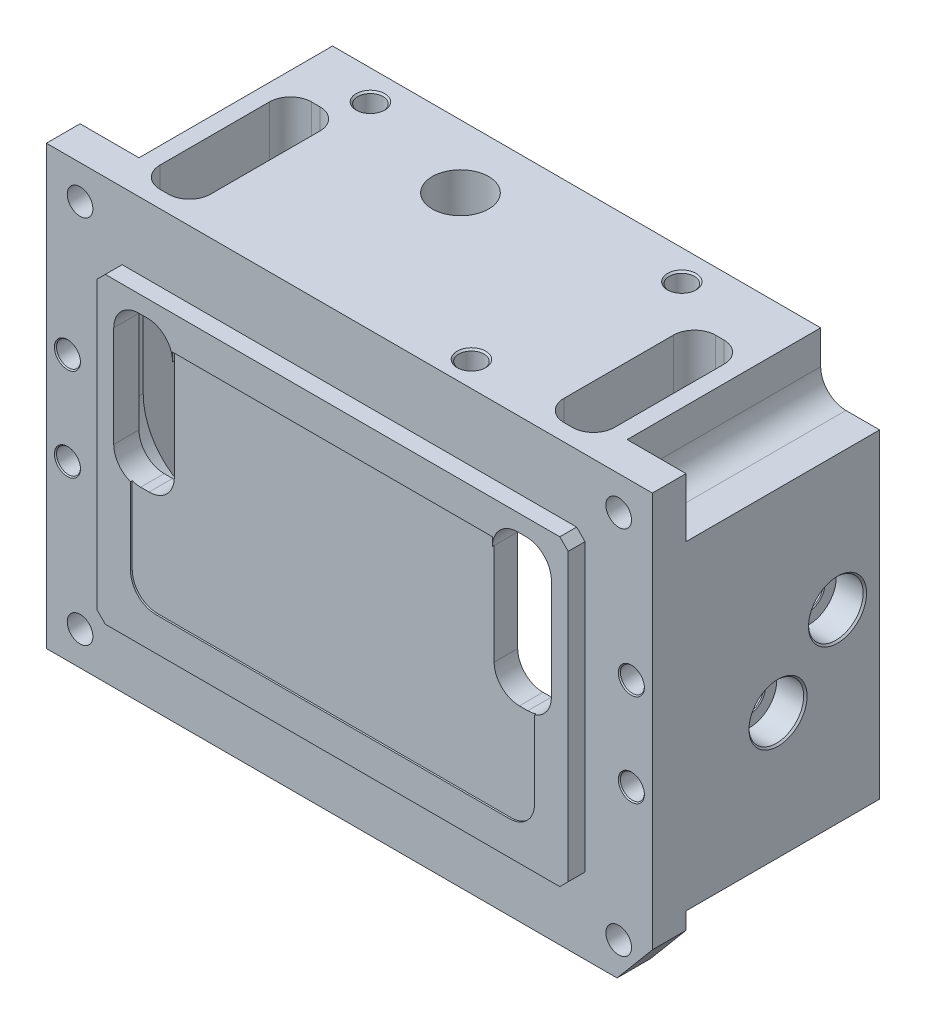
SolidWorks part; units mm, degrees
note: The reader was unsure of these and kept them because the rebuilt part matched: shared geometry of "Эскиз2<3>".
material "2024-T4"
ref_plane "Спереди" through (0, 0, 0) normal (0, 0, 1) x (1, 0, 0)
ref_plane "Сверху" through (0, 0, 0) normal (0, 1, 0) x (1, 0, 0)
ref_plane "Справа" through (0, 0, 0) normal (1, 0, 0) x (0, 0, -1)
sketch "Эскиз1" plane through (0, 0, 0) normal (0, 0, 1) x (1, 0, 0)
  line L1 (-36, -26) -> (36, -26)
  line L2 (-36, -26) -> (-36, 26)
  line L3 (-36, 26) -> (36, 26)
  line L4 (36, -26) -> (36, 26)
  dimension "D1" = 72
  dimension "D2" = 52
  dimension "D3" = 26
  dimension "D4" = 36
extrude "Вытянуть1" add sketch "Эскиз1" along normal blind 29
hole_wizard "Цековка для  винта с внутренним шестигранником #41" positions "Эскиз14" profile "Эскиз13" counterbore size "#4" standard "Ansi (в дюймах)" end condition through all
sketch "Эскиз14" plane through (0, 0, 0) normal (0, 0, -1) x (-1, 0, 0)
  point P0 (-32, -22)
  point P1 (-32, 22)
  point P3 (32, 22)
  point P5 (32, -22)
  dimension "D1" = 64
  dimension "D2" = 44
  dimension "D3" = 22
  dimension "D4" = 32
sketch "Эскиз13" plane through (32, -22, 0) normal (1, 0, 0) x (0, 1, 0)
  line L0 (0, 0) -> (0, 29)
  line L1 (0, 29) -> (1.524, 29)
  line L3 (1.524, 29) -> (1.524, 17.5768)
  line L4 (1.524, 17.5768) -> (2.54, 17.5768)
  line L5 (2.54, 17.5768) -> (2.54, 0)
  line L7 (2.54, 0) -> (0, 0)
  line L11 (0, -6.35) -> (0, 107.95) construction
  dimension "Диаметр сквозного отверстия" = 3.048
  dimension "Глубина сквозного отверстия" = 29
  dimension "Диаметр цековки" = 5.08
  dimension "Глубина цековки" = 17.5768
sketch "Эскиз2" plane through (0, 0, 0) normal (0, 0, -1) x (-1, 0, 0)
  line L0 (-5.5, 12) -> (-5.5, 1)
  line L1 (-22.5, -20) -> (22.5, -20)
  line L2 (-30.5, -12) -> (-30.5, 12)
  line L3 (-22.5, 20) -> (22.5, 20)
  line L4 (30.5, -12) -> (30.5, 12)
  line L5 (-13.5, -7) -> (-21.5, -7)
  line L6 (5.5, 12) -> (5.5, 1)
  line L7 (13.5, -7) -> (21.5, -7)
  line L8 (29.5, 12) -> (29.5, 1)
  line L9 (-29.5, 12) -> (-29.5, 1)
  arc A0 (-22.5, 20) -> (-30.5, 12) centre (-22.5, 12) ccw
  arc A1 (30.5, 12) -> (22.5, 20) centre (22.5, 12) ccw
  arc A2 (22.5, -20) -> (30.5, -12) centre (22.5, -12) ccw
  arc A3 (-30.5, -12) -> (-22.5, -20) centre (-22.5, -12) ccw
  arc A4 (5.5, 12) -> (13.5, 20) centre (13.5, 12) cw
  arc A5 (-5.5, 12) -> (-13.5, 20) centre (-13.5, 12) ccw
  arc A6 (-5.5, 1) -> (-13.5, -7) centre (-13.5, 1) cw
  arc A7 (-21.5, -7) -> (-29.5, 1) centre (-21.5, 1) cw
  arc A8 (5.5, 1) -> (13.5, -7) centre (13.5, 1) ccw
  arc A9 (21.5, -7) -> (29.5, 1) centre (21.5, 1) ccw
  arc A10 (-21.5, 20) -> (-29.5, 12) centre (-21.5, 12) ccw
  arc A11 (21.5, 20) -> (29.5, 12) centre (21.5, 12) cw
  dimension "D5" = 8
  dimension "D1" = 30.5
  dimension "D2" = 30.5
  dimension "D3" = 20
  dimension "D4" = 20
  dimension "D6" = 25
  dimension "D7" = 25
  dimension "D8" = 27
  dimension "D9" = 1
  dimension "D10" = 1
extrude "Вырез-Вытянуть1" cut sketch "Эскиз2" against normal offset from surface (22 mm away) 7 contours A7 L5 A6 L0 A5 L3 A0 L2 | A9 L7 A8 L6 A4 L3 A5 L0 A6 L5 A7 L2 A3 L1 A2 L4 | L7 A9 L4 A1 L3 A4 L6 A8 up to face at (30.476, -22, 29)
extrude "Вырез-Вытянуть15" cut sketch "Эскиз2<3>" against normal offset from surface (26 mm away) 3 contours A7 L5 A6 L0 A5 L3 A0 L2 | L7 A9 L4 A1 L3 A4 L6 A8 up to face at (30.476, -22, 29)
sketch "Эскиз2<3>" plane through (0, 0, 0) normal (0, 0, -1) x (-1, 0, 0) same geometry as "Эскиз2"
sketch "Эскиз3" plane through (0, 26, 0) normal (0, 1, 0) x (-1, 0, 0)
  line L0 (0, 0) -> (0, 30) construction
  line L1 (-24.5, 25) -> (-23.5, 25)
  line L2 (-27, 22.5) -> (-27, 9.5)
  line L3 (-24.5, 7) -> (-23.5, 7)
  line L4 (-21, 22.5) -> (-21, 9.5)
  line L5 (21, 22.5) -> (21, 9.5)
  line L6 (23.5, 7) -> (24.5, 7)
  line L7 (27, 22.5) -> (27, 9.5)
  line L8 (23.5, 25) -> (24.5, 25)
  line L10 (-36, 29) -> (36, 29) construction
  arc A0 (-24.5, 25) -> (-27, 22.5) centre (-24.5, 22.5) ccw
  arc A1 (-21, 22.5) -> (-23.5, 25) centre (-23.5, 22.5) ccw
  arc A2 (-23.5, 7) -> (-21, 9.5) centre (-23.5, 9.5) ccw
  arc A3 (-27, 9.5) -> (-24.5, 7) centre (-24.5, 9.5) ccw
  arc A4 (21, 9.5) -> (23.5, 7) centre (23.5, 9.5) ccw
  arc A5 (27, 22.5) -> (24.5, 25) centre (24.5, 22.5) ccw
  arc A6 (24.5, 7) -> (27, 9.5) centre (24.5, 9.5) ccw
  arc A7 (23.5, 25) -> (21, 22.5) centre (23.5, 22.5) ccw
  point P7 (-27, 25)
  point P12 (-21, 7)
  point P15 (-27, 7)
  dimension "D12" = 2.5
  dimension "D1" = 21
  dimension "D3" = 18
  dimension "D4" = 6
  dimension "D7" = 4
  dimension "D9" = 6
  dimension "D10" = 18
  dimension "D11" = 21
extrude "Вырез-Вытянуть2" cut sketch "Эскиз3" against normal blind 12
hole_wizard "Цековка для винта с внутренним шестигранником M31" positions "Эскиз9" profile "Эскиз8" counterbore size "M3" standard "DIN" end condition up to next
sketch "Эскиз9" plane through (36, 0, 0) normal (1, 0, 0) x (0, 0, -1)
  line L0 (-29, -26) -> (-29, 26) construction
  line L1 (-29, 26) -> (0, 26) construction
  point P1 (-5, 3)
  point P4 (-12.07, -4.07)
  dimension "D1" = 24
  dimension "D2" = 23
  dimension "D3" = 7.07
  dimension "D4" = 7.07
sketch "Эскиз8" plane through (36, 3, 5) normal (0, 1, 0) x (0, 0, -1)
  line L0 (0, 0) -> (0, 5.5)
  line L1 (1.8, 5.4) -> (1.9, 5.5)
  line L2 (1.8, 5.4) -> (1.8, 3.5)
  line L3 (1.8, 3.5) -> (1.9, 3.4)
  line L4 (1.9, 3.4) -> (3.25, 3.4)
  line L5 (3.25, 3.4) -> (3.25, 0.2)
  line L6 (3.25, 0.2) -> (3.45, 0)
  line L7 (3.45, 0) -> (0, 0)
  line L8 (-3.25, 0.2) -> (-3.45, 0) construction
  line L9 (-1.8, 3.5) -> (-1.9, 3.4) construction
  line L11 (0, -6.35) -> (0, 107.95) construction
  line L12 (1.9, 5.5) -> (0, 5.5)
  line L13 (-1.8, 5.4) -> (-1.9, 5.5) construction
  dimension "Диаметр сквозного отверстия" = 3.6
  dimension "Глубина сквозного отверстия" = 5.5
  dimension "Диаметр цековки" = 6.5
  dimension "Глубина цековки" = 3.4
  dimension "Диаметр передней зенковки" = 6.9
  dimension "Угол передней зенковки" = 90
  dimension "Диаметр средней зенковки" = 3.8
  dimension "Угол средней зенковки" = 90
  dimension "Диаметр задней зенковки" = 3.8
  dimension "Угол задней зенковки" = 90
hole_wizard "Цековка для винта с внутренним шестигранником M32" positions "Эскиз12" profile "Эскиз11" counterbore size "M3" standard "DIN" end condition up to next
sketch "Эскиз12" plane through (-36, 0, 0) normal (-1, 0, 0) x (0, 0, 1)
  line L0 (29, 26) -> (29, -26) construction
  line L2 (29, 26) -> (0, 26) construction
  point P1 (5, 0.5)
  point P4 (12.07, -6.57)
  dimension "D1" = 24
  dimension "D2" = 7.07
  dimension "D3" = 7.07
  dimension "D4" = 25.5
sketch "Эскиз11" plane through (-36, 0.5, 5) normal (0, 1, 0) x (0, 0, 1)
  line L0 (0, 0) -> (0, 5.5)
  line L1 (1.8, 5.4) -> (1.9, 5.5)
  line L2 (1.8, 5.4) -> (1.8, 3.5)
  line L3 (1.8, 3.5) -> (1.9, 3.4)
  line L4 (1.9, 3.4) -> (3.25, 3.4)
  line L5 (3.25, 3.4) -> (3.25, 0.2)
  line L6 (3.25, 0.2) -> (3.45, 0)
  line L7 (3.45, 0) -> (0, 0)
  line L8 (-3.25, 0.2) -> (-3.45, 0) construction
  line L9 (-1.8, 3.5) -> (-1.9, 3.4) construction
  line L11 (0, -6.35) -> (0, 107.95) construction
  line L12 (1.9, 5.5) -> (0, 5.5)
  line L13 (-1.8, 5.4) -> (-1.9, 5.5) construction
  dimension "Диаметр сквозного отверстия" = 3.6
  dimension "Глубина сквозного отверстия" = 5.5
  dimension "Диаметр цековки" = 6.5
  dimension "Глубина цековки" = 3.4
  dimension "Диаметр передней зенковки" = 6.9
  dimension "Угол передней зенковки" = 90
  dimension "Диаметр средней зенковки" = 3.8
  dimension "Угол средней зенковки" = 90
  dimension "Диаметр задней зенковки" = 3.8
  dimension "Угол задней зенковки" = 90
hole_wizard "#4-40 Tapped Hole4" [suppressed] positions "Эскиз16" profile "Эскиз15" tap size "#4-40" standard "Ansi Inch"
sketch "Эскиз16" plane through (0, 0, 32) normal (0, 0, 1) x (1, 0, 0)
  line L0 (-35, -25) -> (35, -25) construction
  line L2 (-35, 25) -> (-35, -25) construction
  line L3 (35, -25) -> (35, 25) construction
  point P0 (-33, 7)
  point P1 (-33, -7)
  point P3 (33, -7)
  point P5 (33, 7)
  dimension "D1" = 14
  dimension "D2" = 18
  dimension "D3" = 2
  dimension "D4" = 2
sketch "Эскиз15" plane through (-33, 7, 32) normal (1, 0, 0) x (0, -1, 0)
  line L0 (0, 0) -> (0, 9.5492)
  line L1 (0, 9.5492) -> (1.1303, 8.87)
  line L2 (1.1303, 8.87) -> (1.1303, 5.69)
  line L3 (1.1303, 5.69) -> (1.4224, 5.69)
  line L5 (1.4224, 5.69) -> (1.4224, 0.2286)
  line L6 (1.4224, 0.2286) -> (1.651, 0)
  line L7 (1.651, 0) -> (0, 0)
  line L8 (-1.4224, 0.2286) -> (-1.651, 0) construction
  line L10 (0, 9.5492) -> (-1.1303, 8.87) construction
  line L11 (0, -6.35) -> (0, 107.95) construction
  dimension "Диаметр сверла" = 2.2606
  dimension "Глубина сверла" = 8.87
  dimension "Диаметр резьбы" = 2.8448
  dimension "Глубина резьбы" = 5.69
  dimension "Диаметр передней зенковки" = 3.302
  dimension "Угол передней зенковки" = 90
  dimension "Угол заточки сверла" = 118
ref_plane "Плоскость1" through (0, -13, -13) normal (0, -0.7071, -0.7071) x (-1, 0, 0)
sketch "Эскиз17" plane through (0, -13, -13) normal (0, -0.7071, -0.7071) x (-1, 0, 0)
  line L0 (-22.5, -14.1421) -> (22.5, -14.1421) construction
  line L2 (36, 18.3848) -> (36, -18.3848) construction
  line L3 (-36, -18.3848) -> (-36, 18.3848) construction
  line L4 (-25.9641, -13.5843) -> (-22.0082, -14.1421)
  line L5 (22.0082, -14.1421) -> (25.9641, -13.5843)
  arc A0 (22.0082, -14.1421) -> (25.9641, -13.5843) centre (24, -13.9617) ccw
  arc A1 (-22.0082, -14.1421) -> (-25.9641, -13.5843) centre (-24, -13.9617) cw
  ellipse E1 centre (22.5, -8.4853) end of major axis (30.5, -8.4853) minor radius 5.6569 (22.5, -14.1421) -> (30.5, -8.4853) ccw construction
  ellipse E2 centre (-22.5, -8.4853) end of major axis (-14.5, -8.4853) minor radius 5.6569 (-30.5, -8.4853) -> (-22.5, -14.1421) ccw construction
  point P14 (24.2793, -15.9421)
  point P18 (-24.2793, -15.9421)
  dimension "D1" = 2
  dimension "D2" = 12
  dimension "D4" = 2
  dimension "D6" = 12
  dimension "D3" = 1.8
  dimension "D5" = 1.8
extrude "Вырез-Вытянуть5" [suppressed] cut sketch "Эскиз17" against normal blind 10
hole_wizard "M3" positions "Эскиз19" profile "Эскиз18" tap size "M3" standard "DIN"
sketch "Эскиз19" plane through (29.5327, 26, -14.0421) normal (0, -1, 0) x (1, 0, 0)
  line L1 (6.4673, 43.0421) -> (6.4673, 14.0421) construction
  line L3 (6.4673, 43.0421) -> (6.4673, 14.0421) construction
  line L7 (-65.5327, 43.0421) -> (6.4673, 43.0421) construction
  point P0 (-50.5327, 17.5421)
  point P1 (-13.5327, 17.5421)
  point P3 (-18.0327, 38.0421)
  dimension "D1" = 5
  dimension "D2" = 37
  dimension "D3" = 20.5
  dimension "D4" = 20
  dimension "D5" = 24.5
sketch "Эскиз18" plane through (-21, 26, 3.5) normal (1, 0, 0) x (0, 0, 1)
  line L0 (0, 0) -> (0, 10.7511)
  line L1 (0, 10.7511) -> (1.25, 10)
  line L2 (1.25, 10) -> (1.25, 8)
  line L3 (1.25, 8) -> (1.5, 8)
  line L5 (1.5, 8) -> (1.5, 0.2)
  line L6 (1.5, 0.2) -> (1.7, 0)
  line L7 (1.7, 0) -> (0, 0)
  line L8 (-1.5, 0.2) -> (-1.7, 0) construction
  line L10 (0, 10.7511) -> (-1.25, 10) construction
  line L11 (0, -6.35) -> (0, 107.95) construction
  dimension "Диаметр сверла" = 2.5
  dimension "Глубина сверла" = 10
  dimension "Диаметр резьбы" = 3
  dimension "Глубина резьбы" = 8
  dimension "Диаметр передней зенковки" = 3.4
  dimension "Угол передней зенковки" = 90
  dimension "Угол заточки сверла" = 118
sketch "Эскиз22" plane through (0, 0, 29) normal (0, 0, 1) x (1, 0, 0)
  line L0 (36, 26) -> (-36, 26) construction
  line L1 (-22, -2) -> (-23, -2)
  line L2 (-19, 1) -> (-19, 13)
  line L3 (-22, 16) -> (-23, 16)
  line L4 (-26, 1) -> (-26, 13)
  line L6 (22, -2) -> (23, -2)
  line L7 (19, 1) -> (19, 13)
  line L8 (22, 16) -> (23, 16)
  line L9 (26, 1) -> (26, 13)
  arc A0 (-26, 1) -> (-23, -2) centre (-23, 1) ccw
  arc A1 (-19, 1) -> (-22, -2) centre (-22, 1) cw
  arc A2 (-22, 16) -> (-19, 13) centre (-22, 13) cw
  arc A3 (-26, 13) -> (-23, 16) centre (-23, 13) cw
  arc A4 (22, 16) -> (19, 13) centre (22, 13) ccw
  arc A5 (26, 13) -> (23, 16) centre (23, 13) ccw
  arc A6 (23, -2) -> (26, 1) centre (23, 1) ccw
  arc A7 (19, 1) -> (22, -2) centre (22, 1) ccw
  dimension "D7" = 3
  dimension "D1" = 7
  dimension "D2" = 18
  dimension "D3" = 19
  dimension "D4" = 38
  dimension "D5" = 28
  dimension "D6" = 7
extrude "Вырез-Вытянуть6" cut sketch "Эскиз22" against normal through all
ref_plane "Плоскость2" through (0, -22.9586, -8.3562) normal (0, -0.9397, -0.342) x (1, 0, 0)
sketch "Эскиз24" plane through (0, -22.9586, -8.3562) normal (0, -0.9397, -0.342) x (1, 0, 0)
  line L0 (-36, 8.8925) -> (36, 8.8925) construction
  line L1 (-22, 28.8925) -> (-21, 28.8925)
  line L2 (-25, 25.8925) -> (-25, 18.8925)
  line L3 (-22, 15.8925) -> (-21, 15.8925)
  line L4 (-18, 25.8925) -> (-18, 18.8925)
  line L5 (23, 28.8925) -> (24, 28.8925)
  line L6 (20, 25.8925) -> (20, 18.8925)
  line L7 (23, 15.8925) -> (24, 15.8925)
  line L8 (27, 25.8925) -> (27, 18.8925)
  line L9 (36, 36.1436) -> (36, 8.8925) construction
  arc A0 (-22, 28.8925) -> (-25, 25.8925) centre (-22, 25.8925) ccw
  arc A1 (-18, 25.8925) -> (-21, 28.8925) centre (-21, 25.8925) ccw
  arc A2 (-21, 15.8925) -> (-18, 18.8925) centre (-21, 18.8925) ccw
  arc A3 (-25, 18.8925) -> (-22, 15.8925) centre (-22, 18.8925) ccw
  arc A4 (20, 18.8925) -> (23, 15.8925) centre (23, 18.8925) ccw
  arc A5 (23, 28.8925) -> (20, 25.8925) centre (23, 25.8925) ccw
  arc A6 (27, 25.8925) -> (24, 28.8925) centre (24, 25.8925) ccw
  arc A7 (24, 15.8925) -> (27, 18.8925) centre (24, 18.8925) ccw
  dimension "D1" = 3
  dimension "D2" = 13
  dimension "D3" = 7
  dimension "D4" = 38
  dimension "D5" = 7
  dimension "D6" = 7
  dimension "D7" = 9
extrude "Вырез-Вытянуть7" [suppressed] cut sketch "Эскиз24" against normal blind 49
sketch "Эскиз25" plane through (0, 0, 0) normal (0, 0, -1) x (-1, 0, 0)
  line L0 (36, -26) -> (-36, -26) construction
  line L1 (-36, -26) -> (-36, 26) construction
  line L2 (-21, -22) -> (-36, -22) construction
  arc A0 (-26.6569, -26) -> (-15.3431, -26) centre (-21, -28) cw
  dimension "D1" = 6
  dimension "D2" = 15
  dimension "D3" = 4
extrude "Вырез-Вытянуть8" [suppressed] cut sketch "Эскиз25" against normal through all
sketch "Эскиз29" plane through (0, 0, 0) normal (0, 0, -1) x (-1, 0, 0)
  line L0 (29, 26) -> (29, 22)
  line L2 (32, 19) -> (36, 19)
  line L4 (-36, 0.05) -> (36, 0) construction
  line L5 (0, 26) -> (0, -26) construction
  line L7 (32, -19) -> (36, -19)
  line L8 (29, -26) -> (29, -22)
  line L9 (-29, -26) -> (-29, -22)
  line L10 (-32, -19) -> (-36, -19)
  line L11 (-32, 19) -> (-36, 19)
  line L12 (-29, 26) -> (-29, 22)
  line L14 (-36, 26) -> (36, 26) construction
  line L15 (-36, -26) -> (-36, 26) construction
  line L16 (36, 26) -> (36, -26) construction
  line L17 (36, -26) -> (-36, -26) construction
  arc A0 (32, 19) -> (29, 22) centre (32, 22) cw
  arc A1 (32, -19) -> (29, -22) centre (32, -22) ccw
  arc A2 (-32, -19) -> (-29, -22) centre (-32, -22) cw
  arc A3 (-32, 19) -> (-29, 22) centre (-32, 22) ccw
  dimension "D1" = 7
  dimension "D3" = 3
  dimension "D2" = 7
extrude "Вырез-Вытянуть10" cut sketch "Эскиз29" against normal offset from surface (23 mm away) 6
chamfer "Фаска1" distance 5 angle 40 1 edges at (36, -26, 26) first distance on face at (36, -4.07, 8.62)
sketch "Эскиз26" plane through (0, 26, 0) normal (0, 1, 0) x (1, 0, 0)
  line L0 (-27.5, 0) -> (-27.5, -15)
  line L1 (29, 0) -> (-29, 0) construction
  line L2 (-30.5, -18) -> (-36, -18)
  line L3 (-36, -29) -> (-36, -23) construction
  arc A0 (-30.5, -18) -> (-27.5, -15) centre (-30.5, -15) ccw
  line M8 (-27, -22.5) -> (-27, -9.5)
  arc M9 (-27, -9.5) -> (-24.5, -7) centre (-24.5, -9.5) cw
  line M20 (29, 0) -> (-29, 0)
  line M21 (-36, -23) -> (-36, -29)
  dimension "D1" = 3
  dimension "D2" = 8.5
  dimension "D3" = 18
extrude "Вырез-Вытянуть9" [suppressed] cut sketch "Эскиз26" against normal blind 2.5 contours L2 A0 L0 M8 M9 M20 M21
sketch "Эскиз30" plane through (0, 0, 29) normal (0, 0, 1) x (1, 0, 0)
  line L0 (-21, 14) -> (-21, -1)
  line L1 (-21, -1) -> (-24, -1)
  line L2 (-24, -1) -> (-24, -11)
  line L3 (-21, -14) -> (21, -14)
  line L4 (24, -11) -> (24, -1)
  line L5 (24, -1) -> (21, -1)
  line L6 (21, -1) -> (21, 14)
  line L7 (21, 14) -> (0, 14)
  line L8 (0, 14) -> (-21, 14)
  arc A0 (24, -11) -> (21, -14) centre (21, -11) cw
  arc A1 (-21, -14) -> (-24, -11) centre (-21, -11) cw
  line M6 (19, 1) -> (19, 14)
  arc M11 (26, 1) -> (23, -2) centre (23, 1) cw
  line M12 (23, -2) -> (22, -2)
  arc M13 (22, -2) -> (19, 1) centre (22, 1) cw
  line M14 (-22, -2) -> (-23, -2)
  arc M15 (-23, -2) -> (-26, 1) centre (-23, 1) cw
  line M20 (-19, 14) -> (-19, 1)
  arc M21 (-19, 1) -> (-22, -2) centre (-22, 1) cw
  dimension "D6" = 3
  dimension "D1" = 21
  dimension "D2" = 14
  dimension "D3" = 14
  dimension "D4" = 24
  dimension "D5" = 15
extrude "Вырез-Вытянуть16" cut sketch "Эскиз30" against normal blind 0.2 contours A1 L3 A0 L4 L7 L8 L2 M11 M12 M13 M6 M20 M21 M14 M15
sketch "Эскиз31" plane through (0, 0, 29) normal (0, 0, 1) x (1, 0, 0)
  line L0 (-28, 17) -> (-27, 18)
  line L1 (-27, -18) -> (27, -18)
  line L2 (-28, -17) -> (-28, 17)
  line L3 (-27, 18) -> (27, 18)
  line L4 (28, -17) -> (28, 17)
  line L5 (-28, -18) -> (28, 18) construction
  line L6 (-28, 18) -> (28, -18) construction
  line L7 (27, 18) -> (28, 17)
  line L8 (27, -18) -> (28, -17)
  line L9 (-27, -18) -> (-28, -17)
  point P0 (0, 0)
  dimension "D1" = 36
  dimension "D2" = 56
  dimension "D5" = 1
  dimension "D6" = 1
  dimension "D7" = 1
  dimension "D8" = 1
extrude "Вырез-Вытянуть18" cut sketch "Эскиз31" against normal blind 2
hole_wizard "2 Отверстие #4-40" positions "Эскиз28" profile "Эскиз27" tap size "#4-40" standard "Ansi (в дюймах)"
sketch "Эскиз28" plane through (-34.1022, 6.6113, 27) normal (0, 0, 1) x (1, 0, 0)
  line L0 (70.1022, 19.3887) -> (-1.8978, 19.3887) construction
  line L1 (70.1022, -27.6113) -> (70.1022, 19.3887) construction
  line L2 (-1.8978, 19.3887) -> (-1.8978, -32.6113) construction
  point P0 (67.6022, -12.1113)
  point P1 (67.6022, -1.1113)
  point P3 (0.6022, -1.1113)
  point P5 (0.6022, -12.1113)
  dimension "D1" = 11
  dimension "D2" = 20.5
  dimension "D3" = 2.5
  dimension "D4" = 2.5
sketch "Эскиз27" plane through (33.5, -5.5, 27) normal (1, 0, 0) x (0, -1, 0)
  line L0 (0, 0) -> (0, 9.5392)
  line L1 (0, 9.5392) -> (1.1303, 8.86)
  line L2 (1.1303, 8.86) -> (1.1303, 5.69)
  line L3 (1.1303, 5.69) -> (1.4224, 5.69)
  line L5 (1.4224, 5.69) -> (1.4224, 0.127)
  line L6 (1.4224, 0.127) -> (1.5494, 0)
  line L7 (1.5494, 0) -> (0, 0)
  line L8 (-1.4224, 0.127) -> (-1.5494, 0) construction
  line L10 (0, 9.5392) -> (-1.1303, 8.86) construction
  line L11 (0, -6.35) -> (0, 107.95) construction
  dimension "Диаметр сверла" = 2.2606
  dimension "Глубина сверла" = 8.86
  dimension "Диаметр резьбы" = 2.8448
  dimension "Глубина резьбы" = 5.69
  dimension "Диаметр передней зенковки" = 3.0988
  dimension "Угол передней зенковки" = 90
  dimension "Угол заточки сверла" = 118
sketch "Эскиз32" plane through (0, 0, 0) normal (0, 0, -1) x (-1, 0, 0)
  line L1 (-24.9548, -28.6288) -> (25.0452, -28.6288)
  line L2 (-24.9548, -28.6288) -> (-24.9548, -15.0899)
  line L3 (-24.9548, -15.0899) -> (25.0452, -15.0899)
  line L4 (25.0452, -28.6288) -> (25.0452, -15.0899)
  line L5 (-24.9548, -28.6288) -> (25.0452, -15.0899) construction
  line L6 (-24.9548, -15.0899) -> (25.0452, -28.6288) construction
  point P0 (0.0452, -21.8593)
  dimension "D1" = 50
extrude "Вырез-Вытянуть19" cut sketch "Эскиз32" against normal up to surface (22 mm away) up to face at (0, 3.8168, 22)
sketch "Эскиз33" plane through (0, 26, 0) normal (0, 1, 0) x (1, 0, 0)
  line L0 (29, 0) -> (-29, 0) construction
  line L1 (36, -23) -> (36, 0) construction
  circle A0 centre (-6.3, -7.5) radius 3.35
  dimension "D1" = 6.7
  dimension "D2" = 7.5
  dimension "D3" = 42.3
extrude "Вырез-Вытянуть20" cut sketch "Эскиз33" against normal up to next
